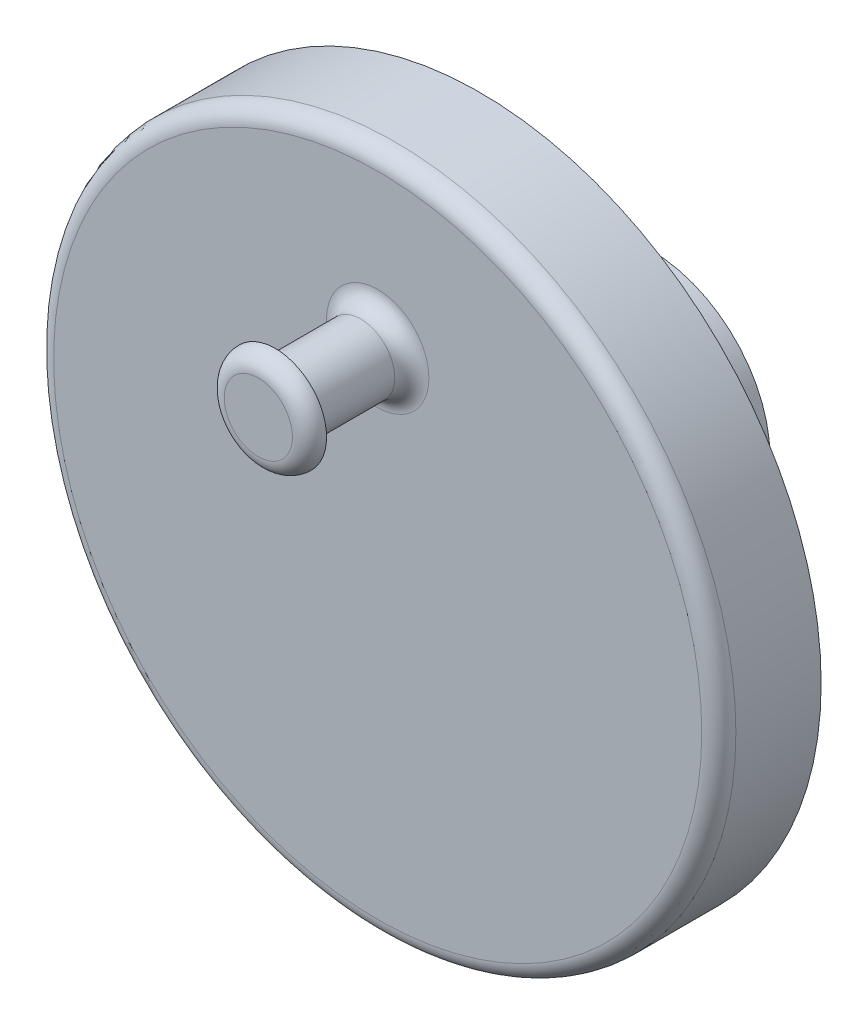
SolidWorks part; units mm, degrees
ref_plane "Front Plane" through (0, 0, 0) normal (0, 0, 1) x (1, 0, 0)
ref_plane "Top Plane" through (0, 0, 0) normal (0, 1, 0) x (1, 0, 0)
ref_plane "Right Plane" through (0, 0, 0) normal (1, 0, 0) x (0, 0, -1)
sketch "Sketch1" plane through (0, 0, 0) normal (0, 0, 1) x (1, 0, 0)
  circle A0 centre (0, 0) radius 20
  dimension "D1" = 40
extrude "Boss-Extrude1" add sketch "Sketch1" along normal blind 6
sketch "Sketch2" plane through (0, 0, 0) normal (0, 0, -1) x (-1, 0, 0)
  circle A0 centre (0, 0) radius 3
  circle A1 centre (0, 0) radius 7
  dimension "D1" = 6
  dimension "D2" = 4
extrude "Boss-Extrude2" add sketch "Sketch2" along normal blind 10
sketch "Sketch3" plane through (0, 0, 6) normal (0, 0, 1) x (1, 0, 0)
  circle A0 centre (0, 10) radius 2
  dimension "D1" = 4
  dimension "D2" = 10
extrude "Boss-Extrude3" add sketch "Sketch3" along normal blind 7
sketch "Sketch4" plane through (0, 0, 13) normal (0, 0, 1) x (1, 0, 0)
  circle A0 centre (0, 10) radius 3
  dimension "D1" = 6
extrude "Boss-Extrude4" add sketch "Sketch4" against normal blind 1
fillet "Fillet1" radius 1 4 edges at (20, 0, 6) (2, 10, 6) (3, 10, 13) (7, 0, 0)
